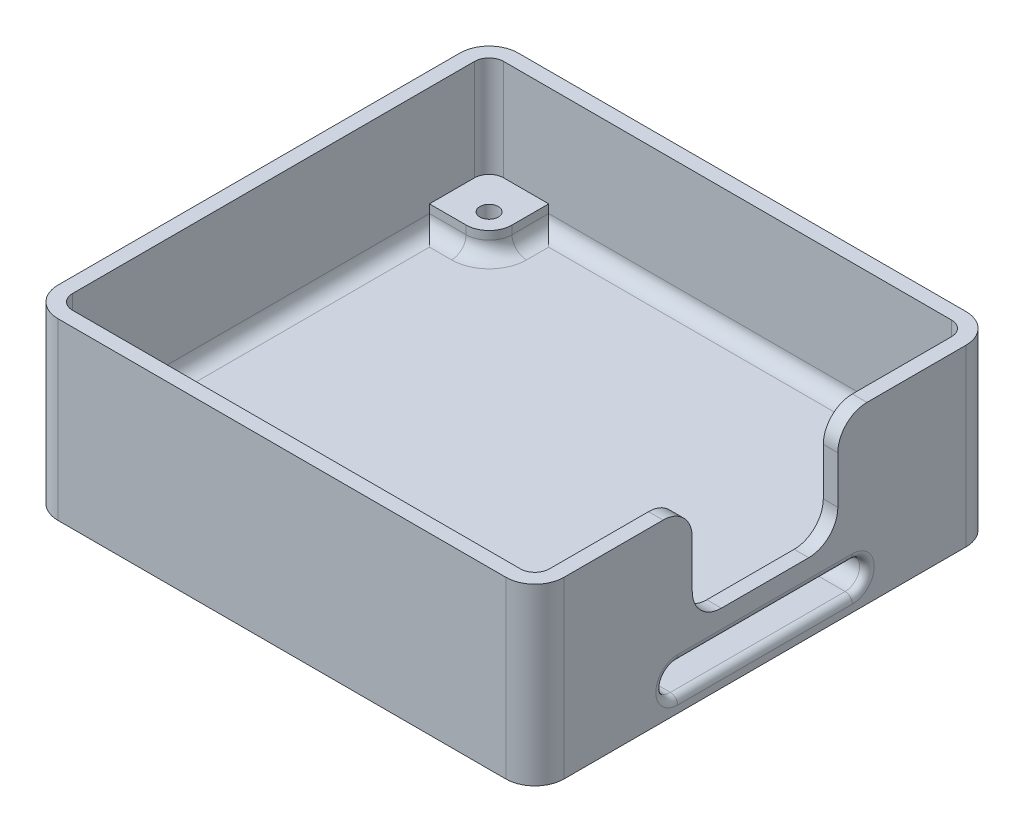
SolidWorks part; units mm, degrees
ref_plane "Front Plane" through (0, 0, 0) normal (0, 0, 1) x (1, 0, 0)
ref_plane "Top Plane" through (0, 0, 0) normal (0, 1, 0) x (1, 0, 0)
ref_plane "Right Plane" through (0, 0, 0) normal (1, 0, 0) x (0, 0, -1)
sketch "Sketch5" plane through (0, 0, 0) normal (0, 1, 0) x (1, 0, 0)
  line L1 (-22, -19.5) -> (22, -19.5) construction
  line L2 (-22, -19.5) -> (-22, 19.5) construction
  line L3 (-22, 19.5) -> (22, 19.5) construction
  line L4 (22, -19.5) -> (22, 19.5) construction
  line L5 (-22, -19.5) -> (22, 19.5) construction
  line L6 (-22, 19.5) -> (22, -19.5) construction
  circle A0 centre (-22, 19.5) radius 1
  circle A1 centre (22, 19.5) radius 1
  circle A2 centre (22, -19.5) radius 1
  circle A3 centre (-22, -19.5) radius 1
  point P0 (0, 0)
  dimension "D3" = 2
  dimension "D1" = 39
  dimension "D2" = 44
sketch "Sketch1" plane through (0, 0, 0) normal (0, 1, 0) x (1, 0, 0)
  line L0 (-26, 19.5) -> (-22, 19.5) construction
  line L1 (-26, -23.5) -> (26, -23.5)
  line L2 (-26, -23.5) -> (-26, 23.5)
  line L3 (-26, 23.5) -> (26, 23.5)
  line L4 (26, -23.5) -> (26, 23.5)
  line L5 (-26, -23.5) -> (26, 23.5) construction
  line L6 (-26, 23.5) -> (26, -23.5) construction
  line L7 (-27.5875, -25.0875) -> (27.5875, -25.0875)
  line L8 (-27.5875, -25.0875) -> (-27.5875, 25.0875)
  line L9 (-27.5875, 25.0875) -> (27.5875, 25.0875)
  line L10 (27.5875, -25.0875) -> (27.5875, 25.0875)
  line L11 (-27.5875, -25.0875) -> (27.5875, 25.0875) construction
  line L12 (-27.5875, 25.0875) -> (27.5875, -25.0875) construction
  line L13 (-22, 19.5) -> (-22, 23.5) construction
  point P0 (0, 0)
  point P6 (0, 0)
  dimension "D1" = 1.5875
  dimension "D2" = 1.5875
  dimension "D3" = 4
extrude "Boss-Extrude1" add sketch "Sketch1" along normal blind 19.05
sketch "Sketch2" plane through (0, 0, 0) normal (0, -1, 0) x (1, 0, 0)
  line L4 (27.5875, -25.0875) -> (27.5875, 25.0875)
  line L5 (27.5875, 25.0875) -> (-27.5875, 25.0875)
  line L6 (-27.5875, 25.0875) -> (-27.5875, -25.0875)
  line L7 (-27.5875, -25.0875) -> (27.5875, -25.0875)
  line L8 (27.5875, -25.0875) -> (27.5875, 25.0875)
  line L9 (27.5875, 25.0875) -> (-27.5875, 25.0875)
  line L10 (-27.5875, 25.0875) -> (-27.5875, -25.0875)
  line L11 (-27.5875, -25.0875) -> (27.5875, -25.0875)
  dimension "D1" = 0
extrude "Boss-Extrude2" add sketch "Sketch2" against normal blind 0.7937 from offset 4.7625 offset against normal yes
sketch "Sketch4" plane through (26, 0, 0) normal (-1, 0, 0) x (0, 0, 1)
  line L4 (23.5, 4.7625) -> (-23.5, 4.7625)
  line L5 (-23.5, 4.7625) -> (-23.5, 0)
  line L6 (-23.5, 0) -> (23.5, 0)
  line L7 (23.5, 0) -> (23.5, 4.7625)
  line L8 (23.5, 4.7625) -> (-23.5, 4.7625)
  line L9 (-23.5, 4.7625) -> (-23.5, 0)
  line L10 (-23.5, 0) -> (23.5, 0)
  line L11 (23.5, 0) -> (23.5, 4.7625)
  dimension "D1" = 0
extrude "Boss-Extrude3" add sketch "Sketch4" along normal blind 9.525
mirror "Mirror1" about plane through (0, 0, 0) normal (1, 0, 0) of "Boss-Extrude3"
extrude "Cut-Extrude3" cut sketch "Sketch5" against normal through all and the other way through all
sketch "Sketch3" plane through (27.5875, 0, 0) normal (1, 0, 0) x (0, 0, -1)
  line L0 (-9.525, 3.175) -> (9.525, 3.175) construction
  line L1 (-9.525, 4.7625) -> (9.525, 4.7625)
  line L2 (-9.525, 1.5875) -> (9.525, 1.5875)
  line L3 (0, 6.35) -> (0, 0) construction
  line L6 (23.5, 4.7625) -> (-23.5, 4.7625) construction
  arc A0 (-9.525, 4.7625) -> (-9.525, 1.5875) centre (-9.525, 3.175) ccw
  arc A1 (9.525, 1.5875) -> (9.525, 4.7625) centre (9.525, 3.175) ccw
  point P2 (0, 3.175)
  dimension "D1" = 3.175
  dimension "D2" = 19.05
extrude "Cut-Extrude1" cut sketch "Sketch3" against normal through all
sketch "Sketch6" plane through (0, 5.5563, 0) normal (0, 1, 0) x (1, 0, 0)
  line L0 (22, -17) -> (26, -17)
  line L1 (26, 23.5) -> (26, -23.5) construction
  line L2 (26, -17) -> (26, -23.5)
  line L3 (26, -23.5) -> (19.5, -23.5)
  line L4 (-26, -23.5) -> (26, -23.5) construction
  line L5 (19.5, -23.5) -> (19.5, -19.5)
  arc A0 (19.5, -19.5) -> (22, -17) centre (22, -19.5) cw
  circle A1 centre (22, -19.5) radius 1 construction
  circle A2 centre (22, -19.5) radius 1
  dimension "D1" = 1.5
extrude "Boss-Extrude4" add sketch "Sketch6" along normal blind 2.5
mirror "Mirror2" about plane through (0, 0, 0) normal (1, 0, 0) of "Boss-Extrude4"
mirror "Mirror3" about plane through (0, 0, 0) normal (0, 0, 1) of "Boss-Extrude4", "Mirror2"
fillet "Fillet3" radius 1.5875 30 edges at (26, 13.5531, -23.5) (0, 4.7625, -23.5) (-26, 13.5531, -23.5) (26, 13.5531, 23.5) (0, 4.7625, 23.5) (-26, 13.5531, 23.5) (0, 5.5563, 23.5) (-26, 5.5563, 0) (0, 5.5563, -23.5) (26, 5.5563, 0) (-16.475, 4.7625, -16.5125) (-16.475, 2.3812, -23.5) (-16.475, 2.3813, 23.5) (-16.475, 4.7625, 16.5125) (16.475, 4.7625, 16.5125) (16.475, 2.3812, 23.5) (16.475, 2.3813, -23.5) (16.475, 4.7625, -16.5125) (19.5, 5.5563, -21.5) (20.2322, 5.5563, -17.7322) (24, 5.5563, -17) (24, 5.5563, 17) (20.2322, 5.5563, 17.7322) (19.5, 5.5563, 21.5) (-19.5, 5.5563, 21.5) (-20.2322, 5.5563, 17.7322) (-24, 5.5563, 17) (-24, 5.5563, -17) (-20.2322, 5.5563, -17.7322) (-19.5, 5.5563, -21.5)
fillet "Fillet4" radius 3.175 4 edges at (-27.5875, 9.525, 25.0875) (-27.5875, 9.525, -25.0875) (27.5875, 9.525, -25.0875) (27.5875, 9.525, 25.0875)
fillet "Fillet5" radius 0.7937 18 edges at (-27.5875, 4.7625, 0) (27.5875, 4.7625, 0) (-27.5875, 3.175, 11.1125) (-27.5875, 3.175, -11.1125) (27.5875, 3.175, 11.1125) (27.5875, 3.175, -11.1125) (-27.5875, 1.5875, 0) (27.5875, 1.5875, 0) (16.01, 4.2975, -10.6475) (16.475, 2.0525, -10.6475) (16.475, 1.5875, 0) (16.475, 2.0525, 10.6475) (-16.01, 4.2975, -10.6475) (-16.475, 2.0525, -10.6475) (-16.475, 1.5875, 0) (-16.475, 2.0525, 10.6475) (16.01, 4.2975, 10.6475) (-16.01, 4.2975, 10.6475)
sketch "Sketch7" plane through (27.5875, 0, 0) normal (1, 0, 0) x (0, 0, -1)
  line L0 (-21.9125, 19.05) -> (21.9125, 19.05) construction
  line L1 (-11.1125, 19.05) -> (0, 19.05)
  line L2 (0, 19.05) -> (0, 7.5563)
  line L3 (0, 7.5563) -> (-4.7625, 7.5563)
  line L4 (-7.9375, 15.875) -> (-7.9375, 10.7313)
  line L5 (-15.4125, 5.5563) -> (15.4125, 5.5563) construction
  arc A0 (-11.1125, 19.05) -> (-7.9375, 15.875) centre (-11.1125, 15.875) cw
  arc A1 (-7.9375, 10.7313) -> (-4.7625, 7.5563) centre (-4.7625, 10.7313) ccw
  point P8 (0, 0)
  point P11 (0, 0)
  point P12 (0, 0)
  point P16 (-6.995, 11.9062)
  point P17 (0, 0)
  point P18 (-7.4889, 15.6914)
  point P19 (-8.923, 16.2013)
  dimension "D2" = 3.175
  dimension "D1" = 2
  dimension "D3" = 7.9375
extrude "Cut-Extrude4" cut sketch "Sketch7" against normal up to next
mirror "Mirror4" about plane through (-27.5885, 19.05, 0) normal (0, 0, -1) of "Cut-Extrude4"
equation "\"wall_thicknes\"= 1 / 16"
equation "\"D1@Sketch1\"=\"wall_thicknes\""
equation "\"D2@Sketch1\"=\"wall_thicknes\""
equation "\"D1@Boss-Extrude2\"=\"wall_thicknes\"/2"
equation "\"w\"=0.0625"
